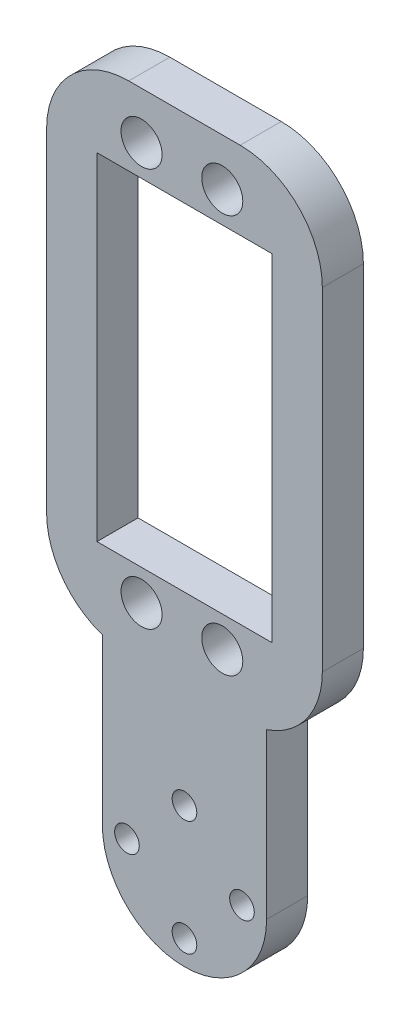
SolidWorks part; units mm, degrees
ref_plane "Front Plane" through (0, 0, 0) normal (0, 0, 1) x (1, 0, 0)
ref_plane "Top Plane" through (0, 0, 0) normal (0, 1, 0) x (1, 0, 0)
ref_plane "Right Plane" through (0, 0, 0) normal (1, 0, 0) x (0, 0, -1)
sketch "Sketch1" plane through (0, 0, 0) normal (0, 0, 1) x (1, 0, 0)
  line L0 (0, 0) -> (0, 80) construction
  line L1 (10, 0) -> (10, 80)
  line L2 (-10, 0) -> (-10, 80)
  line L3 (-10, 80) -> (10, 80)
  circle A0 centre (0, 0) radius 10
  dimension "D1" = 20
  dimension "D4" = 80
  dimension "D2" = 10
  dimension "D3" = 10
extrude "Boss-Extrude1" add sketch "Sketch1" along normal blind 5 contours A0 L0 L3 L2 | L0 A0 L1 L3 | A0 region at (-5.0823, 43.8925, 0) region at (5.0823, 43.8925, 0) region at (6.8711, 6.8711, 0)
sketch "Sketch2" plane through (0, 0, 5) normal (0, 0, 1) x (1, 0, 0)
  line L0 (-10, 0) -> (10, 0) construction
  line L1 (0, 9.5784) -> (0, -14.956) construction
  line L2 (10, 0) -> (10, 80) construction
  circle A0 centre (0, 0) radius 1.5 construction
  circle A1 centre (0, 7) radius 1.5
  circle A2 centre (7, 0) radius 1.5
  circle A3 centre (0, -7) radius 1.5
  circle A4 centre (-7, 0) radius 1.5
  point P22 (0, 0)
  dimension "D1" = 3
  dimension "D2" = 3
  dimension "D3" = 7
  dimension "D4" = 4
extrude "Cut-Extrude1" cut sketch "Sketch2" against normal blind 10
sketch "Sketch3" plane through (0, 0, 5) normal (0, 0, 1) x (1, 0, 0)
  line L0 (0, 0) -> (0, 66.4814) construction
  line L3 (10.65, 70.5) -> (-10.65, 29.5) construction
  line L4 (10.65, 29.5) -> (-10.65, 70.5) construction
  line L5 (0, 20) -> (0, 80) construction
  line L6 (0, 35) -> (0, 65) construction
  line L7 (-10.65, 29.5) -> (-10.65, 70.5)
  line L8 (10.65, 70.5) -> (-10.65, 70.5)
  line L9 (10.65, 29.5) -> (10.65, 70.5)
  line L10 (10.65, 29.5) -> (-10.65, 29.5)
  line L11 (-10, 80) -> (10, 80) construction
  circle A0 centre (0, 60.15) radius 1.25 construction
  circle A1 centre (4.6, 74.25) radius 2.5
  circle A2 centre (-5.2237, 74.25) radius 2.5
  circle A3 centre (-5.2237, 25.75) radius 2.5
  circle A4 centre (4.6, 25.75) radius 2.5
  point P31 (-2.003, 55.5232)
  point P32 (0, 50)
  dimension "D1" = 30
sketch "Sketch4" plane through (0, 0, 5) normal (0, 0, 1) x (1, 0, 0)
  line L1 (-16.78, 80) -> (16.78, 80)
  line L2 (-16.78, 80) -> (-16.78, 20)
  line L3 (-16.78, 20) -> (16.78, 20)
  line L4 (16.78, 80) -> (16.78, 20)
  line L5 (-16.78, 80) -> (16.78, 20) construction
  line L6 (-16.78, 20) -> (16.78, 80) construction
  point P0 (0, 50)
  dimension "D1" = 60
  dimension "D2" = 33.56
extrude "Boss-Extrude2" add sketch "Sketch4" against normal blind 5
fillet "Fillet1" radius 10 4 edges at (16.78, 80, 2.5) (16.78, 20, 2.5) (-16.78, 20, 2.5) (-16.78, 80, 2.5)
extrude "Cut-Extrude2" cut sketch "Sketch3" against normal blind 5
